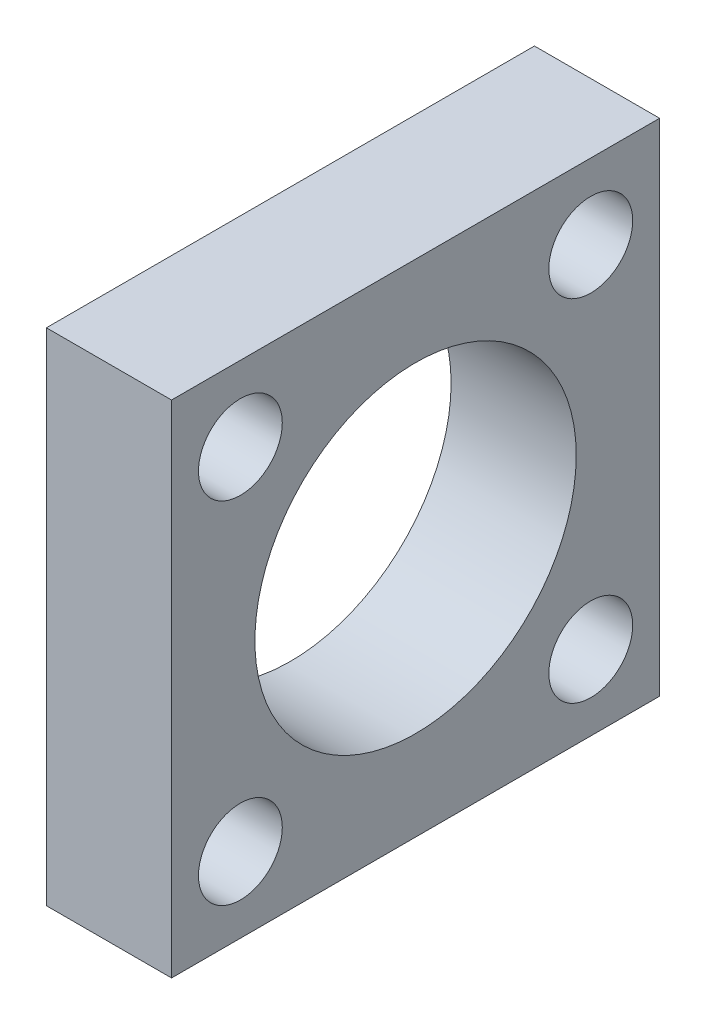
SolidWorks part; units mm, degrees
material "6063-T5"
ref_plane "Front Plane" through (0, 0, 0) normal (0, 0, 1) x (1, 0, 0)
ref_plane "Top Plane" through (0, 0, 0) normal (0, 1, 0) x (1, 0, 0)
ref_plane "Right Plane" through (0, 0, 0) normal (1, 0, 0) x (0, 0, -1)
sketch "Sketch1" plane through (0, 0, 0) normal (1, 0, 0) x (0, 0, -1)
  line L0 (3.4093, 11.0062) -> (3.4093, -28.9938)
  line L1 (-16.0907, 11.0062) -> (22.9093, 11.0062)
  line L2 (-16.0907, 11.0062) -> (-16.0907, -28.9938)
  line L3 (-16.0907, -28.9938) -> (22.9093, -28.9938)
  line L4 (22.9093, 11.0062) -> (22.9093, -28.9938)
  line L5 (-16.0907, -8.9938) -> (22.9093, -8.9938)
  line L7 (-10.5907, -22.9938) -> (17.4093, -22.9938)
  line L8 (-10.5907, -22.9938) -> (-10.5907, 5.0062)
  line L9 (-10.5907, 5.0062) -> (17.4093, 5.0062)
  line L10 (17.4093, -22.9938) -> (17.4093, 5.0062)
  line L11 (-10.5907, -22.9938) -> (17.4093, 5.0062) construction
  line L12 (-10.5907, 5.0062) -> (17.4093, -22.9938) construction
  circle A0 centre (3.4093, -8.9938) radius 12.8397
  circle A1 centre (-10.5907, 5.0062) radius 3.35
  circle A2 centre (17.4093, 5.0062) radius 3.35
  circle A3 centre (17.4093, -22.9938) radius 3.35
  circle A4 centre (-10.5907, -22.9938) radius 3.35
  dimension "D3" = 25.6794
  dimension "D6" = 6.7
  dimension "D1" = 39
  dimension "D2" = 40
  dimension "D4" = 28
  dimension "D5" = 28
extrude "Boss-Extrude1" add sketch "Sketch1" along normal blind 10 contours L1 L4 L3 L2
extrude "SM1 threaded hole" cut sketch "Sketch1<3>" along normal up to next contours A0
sketch "Sketch1<3>" plane through (0, 0, 0) normal (1, 0, 0) x (0, 0, -1) same geometry as "Sketch1"
extrude "oversized 8-32 thru holes" cut sketch "Sketch1<4>" along normal up to next contours A4 | A3 | A2 | A1
sketch "Sketch1<4>" plane through (0, 0, 0) normal (1, 0, 0) x (0, 0, -1) same geometry as "Sketch1"
sketch "Sketch2" plane through (0, -28.9938, 0) normal (0, -1, 0) x (1, 0, 0)
  line L0 (5, 16.0907) -> (5, -22.9093)
  line L3 (10, 16.0907) -> (0, 16.0907) construction
  line L4 (10, -22.9093) -> (0, -22.9093) construction
  circle A0 centre (5, -9.9093) radius 1.725
  dimension "D1" = 3.45
  dimension "D2" = 13
hole_wizard "#8-32 Tapped Hole1" positions "Sketch3" profile "Sketch4" tap size "#8-32" standard "ANSI Inch"
sketch "Sketch3" plane through (0, -28.9938, 0) normal (0, -1, 0) x (-1, 0, 0)
  point P0 (-5, 9.9093)
sketch "Sketch4" plane through (5, -28.9938, -9.9093) normal (1, 0, 0) x (0, 0, -1)
  line L0 (0, 0) -> (0, 7.0378)
  line L1 (0, 7.0378) -> (1.7272, 6)
  line L2 (1.7272, 6) -> (1.7272, 0)
  line L5 (1.7272, 0) -> (0, 0)
  line L10 (0, 7.0378) -> (-1.7272, 6) construction
  line L11 (0, -6.35) -> (0, 107.95) construction
  dimension "Tap Drill Dia." = 3.4544
  dimension "Tap Drill Depth" = 6
  dimension "Drill Angle" = 118
cosmetic thread "Hole Thread1" parameters "D1"=8.33, "D2"=4.1656
